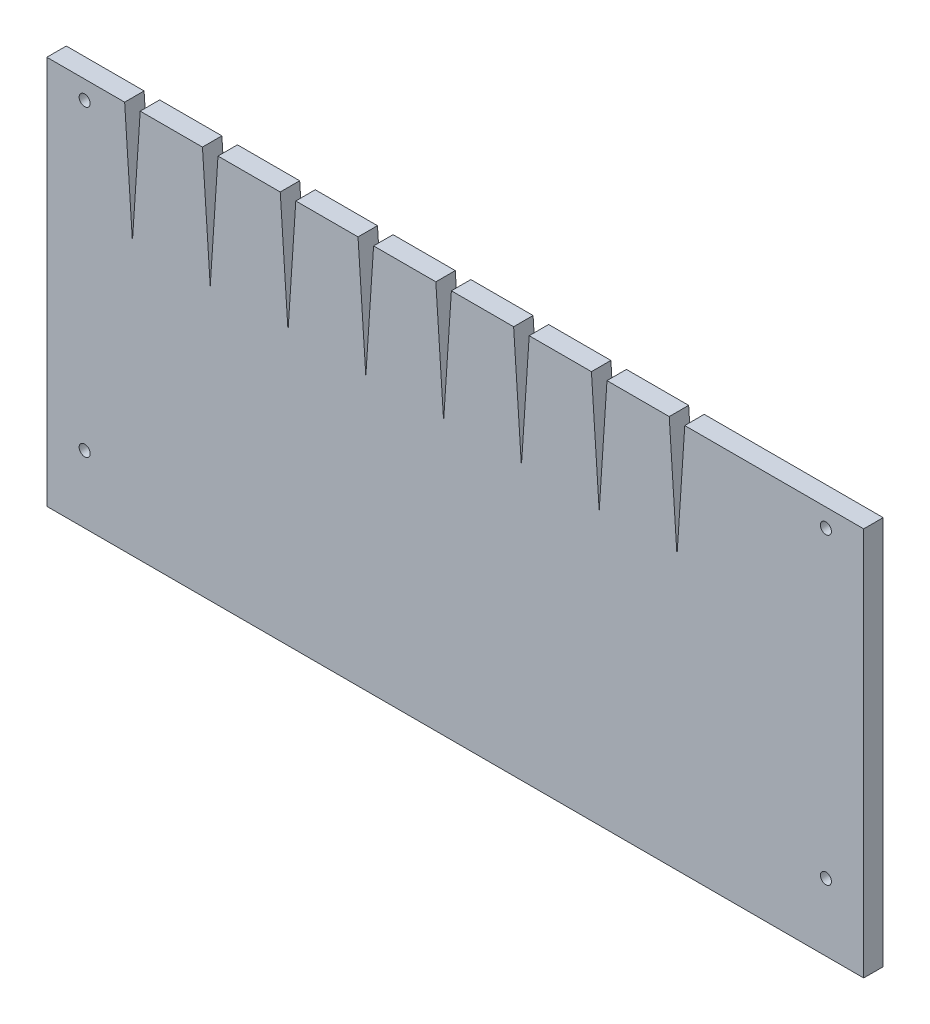
SolidWorks part; units mm, degrees
material "Acrylic (Medium-high impact)"
ref_plane "Front Plane" through (0, 0, 0) normal (0, 0, 1) x (1, 0, 0)
ref_plane "Top Plane" through (0, 0, 0) normal (0, 1, 0) x (1, 0, 0)
ref_plane "Right Plane" through (0, 0, 0) normal (1, 0, 0) x (0, 0, -1)
sketch "Sketch1" plane through (0, 0, 0) normal (0, 0, 1) x (1, 0, 0)
  line L1 (266.7, 127) -> (0, 127)
  line L2 (266.7, 127) -> (266.7, 0)
  line L3 (266.7, 0) -> (0, 0)
  line L4 (0, 127) -> (0, 0)
  line L5 (266.7, 127) -> (0, 0) construction
  line L6 (266.7, 0) -> (0, 127) construction
  point P0 (133.35, 63.5)
  dimension "D1" = 127
  dimension "D2" = 266.7
extrude "Boss-Extrude1" add sketch "Sketch1" along normal blind 6.35
hole_wizard "M3 Clearance Hole1" positions "Sketch2" profile "Sketch3" hole size "M3" standard "ANSI Metric" end condition through all
sketch "Sketch2" plane through (0, 0, 6.35) normal (0, 0, 1) x (1, 0, 0)
  line L0 (0, 127) -> (0, 0) construction
  line L1 (266.7, 127) -> (0, 127) construction
  line L2 (266.7, 0) -> (266.7, 127) construction
  line L3 (0, 0) -> (266.7, 0) construction
  point P0 (12.3444, 121.0056)
  point P2 (12.3444, 21.9964)
  point P4 (254.3556, 21.9964)
  point P6 (254.3556, 121.0056)
  dimension "D1" = 12.3444
  dimension "D2" = 5.9944
  dimension "D3" = 12.3444
  dimension "D4" = 21.9964
sketch "Sketch3" plane through (12.3444, 121.0056, 6.35) normal (1, 0, 0) x (0, -1, 0)
  line L0 (0, 0) -> (0, 6.35)
  line L1 (0, 6.35) -> (1.8, 6.35)
  line L2 (1.8, 6.35) -> (1.8, 0)
  line L5 (1.8, 0) -> (0, 0)
  line L11 (0, -6.35) -> (0, 107.95) construction
  dimension "Thru Hole Dia." = 3.6
  dimension "Thru Hole Depth" = 6.35
sketch "Sketch4" plane through (0, 0, 6.35) normal (0, 0, 1) x (1, 0, 0)
  line L0 (0, 127) -> (0, 0) construction
  line L1 (46.99, 107.95) -> (50.4952, 107.95)
  line L2 (46.99, 107.95) -> (46.99, 31.75)
  line L3 (46.99, 31.75) -> (50.4952, 31.75)
  line L4 (50.4952, 107.95) -> (50.4952, 31.75)
  line L5 (216.2048, 107.95) -> (219.71, 107.95)
  line L6 (216.2048, 107.95) -> (216.2048, 31.75)
  line L7 (216.2048, 31.75) -> (219.71, 31.75)
  line L8 (219.71, 107.95) -> (219.71, 31.75)
  line L9 (266.7, 0) -> (266.7, 127) construction
  line L10 (266.7, 127) -> (0, 127) construction
  dimension "D1" = 3.5052
  dimension "D2" = 76.2
  dimension "D3" = 46.99
  dimension "D4" = 46.99
  dimension "D5" = 19.05
extrude "Cut-Extrude1" [suppressed] cut sketch "Sketch4" against normal through all
sketch "Sketch5" plane through (0, 0, 6.35) normal (0, 0, 1) x (1, 0, 0)
  line L0 (0, 0) -> (266.7, 0)
  line L1 (266.7, 0) -> (266.7, 37.4822)
  line L2 (266.7, 0) -> (266.7, 127) construction
  line L3 (266.7, 37.4822) -> (0, 0)
  dimension "D1" = 8
extrude "Cut-Extrude2" [suppressed] cut sketch "Sketch5" against normal through all
sketch "Sketch6" plane through (0, 0, 6.35) normal (0, 0, 1) x (1, 0, 0)
  line L0 (25.4, 127) -> (27.94, 88.9)
  line L1 (266.7, 127) -> (0, 127) construction
  line L2 (27.94, 88.9) -> (30.48, 127)
  line L3 (30.48, 127) -> (25.4, 127)
  line L4 (0, 127) -> (0, 0) construction
  point P5 (27.94, 127)
  dimension "D1" = 38.1
  dimension "D2" = 5.08
  dimension "D3" = 25.4
extrude "Cut-Extrude3" cut sketch "Sketch6" against normal through all
pattern_linear "LPattern1" count 8 spacing 25.4 along (1, 0, 0) of "Cut-Extrude3"
